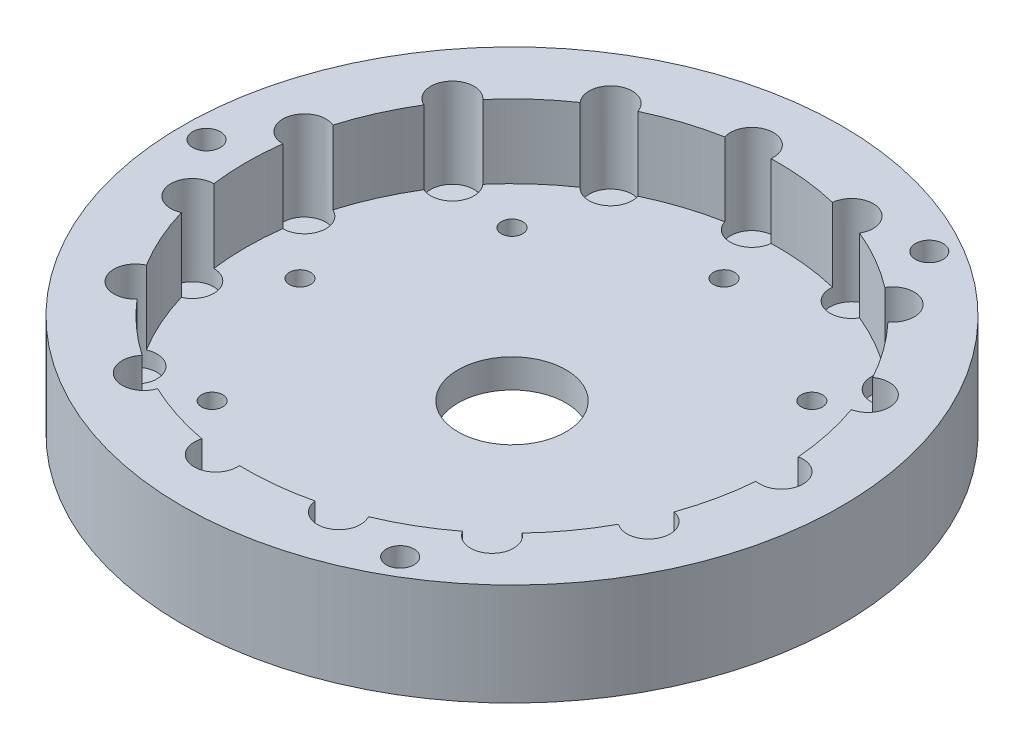
SolidWorks part; units mm, degrees
ref_plane "Front Plane" through (0, 0, 0) normal (0, 0, 1) x (1, 0, 0)
ref_plane "Top Plane" through (0, 0, 0) normal (0, 1, 0) x (1, 0, 0)
ref_plane "Right Plane" through (0, 0, 0) normal (1, 0, 0) x (0, 0, -1)
sketch "Sketch1" plane through (0, 0, 0) normal (0, 1, 0) x (1, 0, 0)
  line L0 (0, 0) -> (-42.5, 0) construction
  circle A0 centre (0, 0) radius 7.5
  circle A1 centre (0, 0) radius 45.85
  circle A2 centre (0, 0) radius 37.5 construction
  circle A3 centre (37.5, 0) radius 3
  circle A4 centre (34.258, 15.2526) radius 3
  circle A5 centre (25.0924, 27.8679) radius 3
  circle A6 centre (11.5881, 35.6646) radius 3
  circle A7 centre (-3.9198, 37.2946) radius 3
  circle A8 centre (-18.75, 32.476) radius 3
  circle A9 centre (-30.3381, 22.0419) radius 3
  circle A10 centre (-36.6805, 7.7967) radius 3
  circle A11 centre (-36.6805, -7.7967) radius 3
  circle A12 centre (-30.3381, -22.0419) radius 3
  circle A13 centre (-18.75, -32.476) radius 3
  circle A14 centre (-3.9198, -37.2946) radius 3
  circle A15 centre (11.5881, -35.6646) radius 3
  circle A16 centre (25.0924, -27.8679) radius 3
  circle A17 centre (34.258, -15.2526) radius 3
  circle A19 centre (0, 0) radius 29.5 construction
  circle A20 centre (29.5, 0) radius 1.48
  circle A21 centre (20.8597, -20.8597) radius 1.48
  circle A22 centre (0, -29.5) radius 1.48
  circle A23 centre (-20.8597, -20.8597) radius 1.48
  circle A24 centre (-29.5, 0) radius 1.48
  circle A25 centre (-20.8597, 20.8597) radius 1.48
  circle A26 centre (0, 29.5) radius 1.48
  circle A27 centre (20.8597, 20.8597) radius 1.48
  arc A28 (36.8833, 2.9359) -> (34.8888, 12.3197) centre (0, 0) ccw
  arc A29 (34.8888, -12.3197) -> (36.8833, -2.9359) centre (0, 0) ccw
  arc A30 (26.8616, -25.4451) -> (32.5004, -17.6839) centre (0, 0) ccw
  arc A31 (14.1898, -34.1709) -> (22.4979, -29.3742) centre (0, 0) ccw
  arc A32 (-0.9355, -36.9882) -> (8.6053, -35.9854) centre (0, 0) ccw
  arc A33 (-15.8991, -33.4099) -> (-6.7752, -36.3744) centre (0, 0) ccw
  arc A34 (-28.1135, -24.0547) -> (-20.9843, -30.4739) centre (0, 0) ccw
  arc A35 (-35.4669, -10.5403) -> (-31.5649, -19.3043) centre (0, 0) ccw
  arc A36 (-36.6878, 4.7967) -> (-36.6878, -4.7967) centre (0, 0) ccw
  arc A37 (-31.5649, 19.3043) -> (-35.4669, 10.5403) centre (0, 0) ccw
  arc A38 (-20.9843, 30.4739) -> (-28.1135, 24.0547) centre (0, 0) ccw
  arc A39 (-6.7752, 36.3744) -> (-15.8991, 33.4099) centre (0, 0) ccw
  arc A40 (8.6053, 35.9854) -> (-0.9355, 36.9882) centre (0, 0) ccw
  arc A41 (22.4979, 29.3742) -> (14.1898, 34.1709) centre (0, 0) ccw
  arc A42 (32.5004, 17.6839) -> (26.8616, 25.4451) centre (0, 0) ccw
  circle A43 centre (-42.5, 0) radius 1.5635
  circle A44 centre (21.25, 36.8061) radius 1.5635
  circle A45 centre (21.25, -36.8061) radius 1.5635
  point P38 (0, 0)
  point P57 (0, 0)
  point P87 (0, 0)
  point P92 (0, 0)
  dimension "D2" = 15
  dimension "D3" = 75
  dimension "D4" = 91.7
  dimension "D5" = 6
  dimension "D8" = 2.96
  dimension "D9" = 59
  dimension "D6" = 37
  dimension "D12" = 3.127
  dimension "D11" = 42.5
  dimension "D1" = 15
  dimension "D7" = 8
  dimension "D10" = 15
  dimension "D13" = 3
extrude "Boss-Extrude1" add sketch "Sketch1" against normal blind 4 contours A4 A42 A5 A41 A6 A40 A7 A39 A8 A38 A9 A37 A10 A36 A11 A35 A12 A34 A13 A33 A14 A32 A15 A31 A16 A30 A17 A29 A3 A28 A0 A20 A21 A22 A23 A24 A25 A26 A27 | A3 | A17 | A4 | A5 | A6 | A7 | A8 | A9 | A10 | A11 | A12 | A13 | A14 | A15 | A16 | A1 A42 A4 A28 A3 A29 A17 A30 A16 A31 A15 A32 A14 A33 A13 A34 A12 A35 A11 A36 A10 A37 A9 A38 A8 A39 A7 A40 A6 A41 A5 | A22 | A23 | A24 | A25 | A26 | A27 | A20 | A21 region at (-44.5532, 0, 0) region at (37.5, 0, 0) region at (33.4543, 0, 0) region at (34.258, 0, -15.2526) region at (34.258, 0, 15.2526) region at (25.0924, 0, -27.8679) region at (25.0924, 0, 27.8679) region at (11.5881, 0, -35.6646) region at (11.5881, 0, 35.6646) region at (-3.9198, 0, -37.2946) region at (-3.9198, 0, 37.2946) region at (-18.75, 0, -32.476) region at (-18.75, 0, 32.476) region at (-30.3381, 0, -22.0419) region at (-30.3381, 0, 22.0419) region at (-36.6805, 0, -7.7967) region at (-36.6805, 0, 7.7967) region at (29.5, 0, 0) region at (20.8597, 0, 20.8597) region at (0, 0, 29.5) region at (-20.8597, 0, 20.8597) region at (-29.5, 0, 0) region at (-20.8597, 0, -20.8597) region at (0, 0, -29.5) region at (20.8597, 0, -20.8597)
extrude "Cut-Extrude1" cut sketch "Sketch1<6>" against normal blind 2.22 contours A24 | A25 | A26 | A27 | A20 | A21 | A22 | A23 | A10 | A11 | A9 | A12 | A13 | A14 | A15 | A16 | A17 | A3 | A4 | A5 | A6 | A7 | A8 region at (37.5, 0, 0) region at (34.258, 0, -15.2526) region at (34.258, 0, 15.2526) region at (25.0924, 0, -27.8679) region at (25.0924, 0, 27.8679) region at (11.5881, 0, -35.6646) region at (11.5881, 0, 35.6646) region at (-3.9198, 0, -37.2946) region at (-3.9198, 0, 37.2946) region at (-18.75, 0, -32.476) region at (-18.75, 0, 32.476) region at (-30.3381, 0, -22.0419) region at (-30.3381, 0, 22.0419) region at (-36.6805, 0, -7.7967) region at (-36.6805, 0, 7.7967) region at (29.5, 0, 0) region at (20.8597, 0, 20.8597) region at (0, 0, 29.5) region at (-20.8597, 0, 20.8597) region at (-29.5, 0, 0) region at (-20.8597, 0, -20.8597) region at (0, 0, -29.5) region at (20.8597, 0, -20.8597)
sketch "Sketch1<6>" plane through (0, 0, 0) normal (0, 1, 0) x (1, 0, 0) same geometry as "Sketch1"
extrude "Boss-Extrude2" add sketch "Sketch1<7>" along normal blind 10.22 contours A1 A42 A4 A28 A3 A29 A17 A30 A16 A31 A15 A32 A14 A33 A13 A34 A12 A35 A11 A36 A10 A37 A9 A38 A8 A39 A7 A40 A6 A41 A5 region at (-44.5532, 0, 0)
sketch "Sketch1<7>" plane through (0, 0, 0) normal (0, 1, 0) x (1, 0, 0) same geometry as "Sketch1"
sketch "Sketch2" plane through (0, 10.22, 0) normal (0, 1, 0) x (1, 0, 0)
  circle A0 centre (-42.5, 0) radius 1.925
  circle A1 centre (21.25, 36.8061) radius 1.925
  circle A2 centre (21.25, -36.8061) radius 1.925
  point P3 (23.5419, 42.0842)
  point P4 (0, 0)
  point P10 (0, 0)
  dimension "D2" = 3.85
  dimension "D1" = 3
extrude "Cut-Extrude2" cut sketch "Sketch2" against normal blind 4
equation "\"bearing_21_OD\"= 21mm"
equation "\"D2@Sketch1\"=\"bearing_15_OD\"+0mm"
equation "\"pin_cirlce_diameter\"= 75mm"
equation "\"D3@Sketch1\"=\"pin_cirlce_diameter\""
equation "\"pin_diam\"= 6mm"
equation "\"D5@Sketch1\"=\"pin_diam\""
equation "\"gear_thickness\"= 4mm"
equation "\"ball_bearing_diam\"= 2.96mm"
equation "\"bearing_21_outer_clearance\"= 0.127mm'change this"
equation "\"bearing_15_OD\"= 15mm"
equation "\"bearing_15_outer_clearance\"= 0mm'change this"
equation "\"D8@Sketch1\"=\"ball_bearing_diam\""
equation "\"D1@Cut-Extrude1\"=\"ball_bearing_diam\"*0.75"
equation "\"thrust_bearing_thickness\"= 5mm'measure this irl and change"
equation "\"D1@Boss-Extrude2\"=\"ball_bearing_diam\"*0.75mm+2*\"gear_thickness\""
